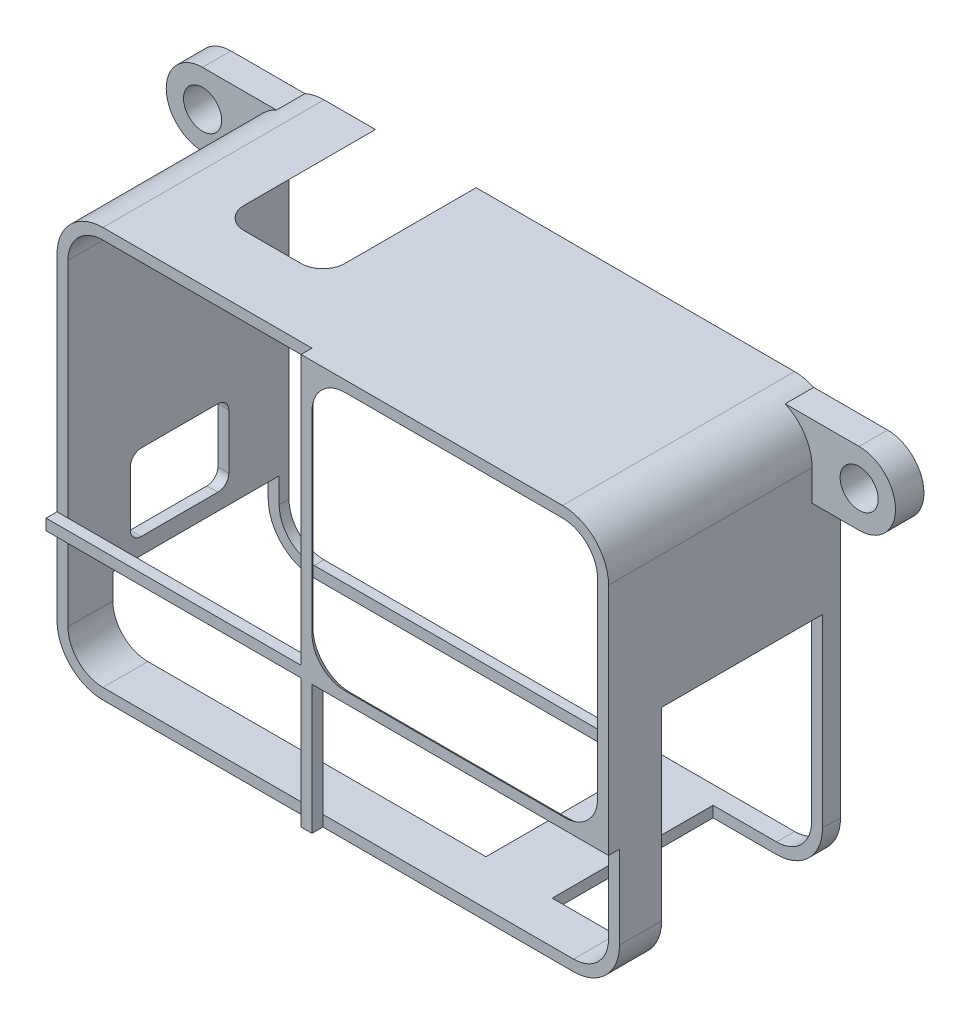
SolidWorks part; units mm, degrees
material "ABS"
ref_plane "Front Plane" through (0, 0, 0) normal (0, 0, 1) x (1, 0, 0)
ref_plane "Top Plane" through (0, 0, 0) normal (0, 1, 0) x (1, 0, 0)
ref_plane "Right Plane" through (0, 0, 0) normal (1, 0, 0) x (0, 0, -1)
sketch "Sketch2" plane through (0, 0, 0) normal (0, 0, 1) x (1, 0, 0)
  line L0 (-27.305, -22.479) -> (27.305, -22.479)
  line L1 (-27.305, -22.225) -> (27.305, -22.225) construction
  line L2 (-31.115, -18.415) -> (-31.115, 18.415) construction
  line L3 (-27.305, 22.225) -> (27.305, 22.225) construction
  line L4 (31.115, -18.415) -> (31.115, 18.415) construction
  line L5 (-31.115, -22.225) -> (31.115, 22.225) construction
  line L6 (-31.115, 22.225) -> (31.115, -22.225) construction
  line L7 (31.369, -18.415) -> (31.369, 18.415)
  line L8 (-27.305, 22.479) -> (27.305, 22.479)
  line L9 (-31.369, -18.415) -> (-31.369, 18.415)
  line L10 (-27.305, -23.749) -> (27.305, -23.749)
  line L11 (32.639, -18.415) -> (32.639, 18.415)
  line L12 (-27.305, 23.749) -> (27.305, 23.749)
  line L13 (-32.639, -18.415) -> (-32.639, 18.415)
  arc A0 (27.305, -22.225) -> (31.115, -18.415) centre (27.305, -18.415) ccw construction
  arc A1 (-27.305, -22.225) -> (-31.115, -18.415) centre (-27.305, -18.415) cw construction
  arc A2 (-31.115, 18.415) -> (-27.305, 22.225) centre (-27.305, 18.415) cw construction
  arc A3 (27.305, 22.225) -> (31.115, 18.415) centre (27.305, 18.415) cw construction
  arc A4 (27.305, -22.479) -> (31.369, -18.415) centre (27.305, -18.415) ccw
  arc A5 (27.305, 22.479) -> (31.369, 18.415) centre (27.305, 18.415) cw
  arc A6 (-31.369, 18.415) -> (-27.305, 22.479) centre (-27.305, 18.415) cw
  arc A7 (-27.305, -22.479) -> (-31.369, -18.415) centre (-27.305, -18.415) cw
  arc A8 (27.305, -23.749) -> (32.639, -18.415) centre (27.305, -18.415) ccw
  arc A9 (27.305, 23.749) -> (32.639, 18.415) centre (27.305, 18.415) cw
  arc A10 (-32.639, 18.415) -> (-27.305, 23.749) centre (-27.305, 18.415) cw
  arc A11 (-27.305, -23.749) -> (-32.639, -18.415) centre (-27.305, -18.415) cw
  point P0 (0, 0)
  dimension "D1" = 3.81
  dimension "D2" = 62.23
  dimension "D3" = 44.45
  dimension "D5" = 1.27
extrude "Boss-Extrude1" add sketch "Sketch2" along normal blind 25.654
sketch "Sketch3" plane through (0, 0, 25.654) normal (0, 0, 1) x (1, 0, 0)
  line L5 (-1.778, 23.749) -> (27.305, 23.749)
  line L6 (-3.048, 23.749) -> (-3.048, -7.493)
  line L7 (27.305, 23.749) -> (-27.305, 23.749) construction
  line L8 (-3.048, -7.493) -> (-32.639, -7.493)
  line L9 (-32.639, 18.415) -> (-32.639, -18.415) construction
  line L11 (-32.639, -8.763) -> (-3.048, -8.763)
  line L12 (-3.048, -8.763) -> (-3.048, -23.749)
  line L13 (-27.305, -23.749) -> (27.305, -23.749) construction
  line L14 (-3.048, -23.749) -> (-1.778, -23.749)
  line L15 (-1.778, -23.749) -> (-1.778, -8.763)
  line L16 (-1.778, -8.763) -> (32.639, -8.763)
  line L17 (32.639, -18.415) -> (32.639, 18.415) construction
  line L18 (32.639, -8.763) -> (32.639, -7.493)
  line L19 (27.559, -7.493) -> (2.032, -7.493)
  line L20 (-1.778, -3.683) -> (-1.778, 18.669)
  line L21 (-1.778, 23.749) -> (-3.048, 23.749)
  line L23 (2.032, 22.479) -> (27.305, 22.479)
  line L26 (-27.305, -23.749) -> (27.305, -23.749)
  line L27 (32.639, -18.415) -> (32.639, 18.415)
  line L28 (27.305, 23.749) -> (-27.305, 23.749)
  line L29 (-32.639, 18.415) -> (-32.639, -18.415)
  line L33 (-32.639, -7.493) -> (-32.639, -8.763)
  line L34 (31.369, 18.415) -> (31.369, -3.683)
  line L36 (32.639, 18.415) -> (32.639, -7.493)
  arc A0 (31.369, 18.415) -> (27.305, 22.479) centre (27.305, 18.415) ccw
  arc A1 (32.639, 18.415) -> (27.305, 23.749) centre (27.305, 18.415) ccw
  arc A2 (31.369, -3.683) -> (27.559, -7.493) centre (27.559, -3.683) cw
  arc A3 (2.032, -7.493) -> (-1.778, -3.683) centre (2.032, -3.683) cw
  arc A4 (-32.639, -18.415) -> (-27.305, -23.749) centre (-27.305, -18.415) ccw
  arc A5 (27.305, -23.749) -> (32.639, -18.415) centre (27.305, -18.415) ccw
  arc A6 (32.639, 18.415) -> (27.305, 23.749) centre (27.305, 18.415) ccw
  arc A7 (-27.305, 23.749) -> (-32.639, 18.415) centre (-27.305, 18.415) ccw
  arc A10 (-1.778, 18.669) -> (2.032, 22.479) centre (2.032, 18.669) cw
  dimension "D6" = 3.81
  dimension "D1" = 1.27
  dimension "D2" = 1.27
  dimension "D3" = 31.242
  dimension "D4" = 34.417
extrude "Boss-Extrude2" add sketch "Sketch3" along normal blind 1.27
sketch "Sketch5" plane through (0, 23.749, 0) normal (0, 1, 0) x (1, 0, 0)
  line L2 (-21.336, 0) -> (-21.336, -15.24)
  line L3 (-18.796, -17.78) -> (-12.192, -17.78)
  line L4 (-9.652, 0) -> (-9.652, -15.24)
  line L5 (-32.639, -25.654) -> (-32.639, 0) construction
  line L6 (27.305, 0) -> (-27.305, 0) construction
  line L7 (-21.336, 0) -> (-9.652, 0)
  arc A0 (-12.192, -17.78) -> (-9.652, -15.24) centre (-12.192, -15.24) ccw
  arc A1 (-21.336, -15.24) -> (-18.796, -17.78) centre (-18.796, -15.24) ccw
  point P7 (-15.494, -17.78)
  point P11 (-9.652, -17.78)
  point P14 (-21.336, -17.78)
  dimension "D4" = 2.54
  dimension "D1" = 11.684
  dimension "D3" = 17.145
  dimension "D2" = 17.78
extrude "Cut-Extrude1" cut sketch "Sketch5" against normal up to next
sketch "Sketch6" plane through (-32.639, 0, 0) normal (-1, 0, 0) x (0, 0, 1)
  line L1 (8.255, -4.699) -> (17.145, -4.699)
  line L2 (6.985, -5.969) -> (6.985, -12.319)
  line L3 (8.255, -13.589) -> (17.145, -13.589)
  line L4 (18.415, -5.969) -> (18.415, -12.319)
  line L6 (25.654, -23.749) -> (0, -23.749) construction
  line L7 (0, 18.415) -> (0, -18.415) construction
  arc A0 (6.985, -12.319) -> (8.255, -13.589) centre (8.255, -12.319) ccw
  arc A1 (8.255, -4.699) -> (6.985, -5.969) centre (8.255, -5.969) ccw
  arc A2 (17.145, -4.699) -> (18.415, -5.969) centre (17.145, -5.969) cw
  arc A3 (17.145, -13.589) -> (18.415, -12.319) centre (17.145, -12.319) ccw
  point P12 (6.985, -4.699)
  point P15 (18.415, -4.699)
  point P18 (18.415, -13.589)
  point P19 (18.415, -9.144)
  point P20 (12.7, -4.699)
  dimension "D5" = 1.27
  dimension "D1" = 11.43
  dimension "D2" = 8.89
  dimension "D3" = 12.7
  dimension "D4" = 14.605
extrude "Cut-Extrude2" cut sketch "Sketch6" against normal up to next
sketch "Sketch7" plane through (0, -23.749, 0) normal (0, -1, 0) x (1, 0, 0)
  line L0 (-32.639, 25.654) -> (-32.639, 0) construction
  line L1 (-32.639, 1.143) -> (11.938, 1.143)
  line L2 (-32.639, 1.143) -> (-32.639, 20.447)
  line L3 (-32.639, 20.447) -> (11.938, 20.447)
  line L4 (11.938, 1.143) -> (11.938, 20.447)
  line L5 (-27.305, 0) -> (27.305, 0) construction
  point P6 (11.938, 10.795)
  dimension "D1" = 44.577
  dimension "D2" = 19.304
  dimension "D3" = 10.795
extrude "Cut-Extrude3" cut sketch "Sketch7" against normal blind 8.255
sketch "Sketch8" plane through (32.639, 0, 0) normal (1, 0, 0) x (0, 0, -1)
  line L0 (-25.654, -23.749) -> (0, -23.749) construction
  line L1 (-20.7645, -23.749) -> (-2.0955, -23.749)
  line L2 (-20.7645, -23.749) -> (-20.7645, 3.048)
  line L3 (-20.7645, 3.048) -> (-2.0955, 3.048)
  line L4 (-2.0955, -23.749) -> (-2.0955, 3.048)
  line L5 (0, -18.415) -> (0, 18.415) construction
  point P6 (-11.43, 3.048)
  dimension "D1" = 18.669
  dimension "D2" = 26.797
  dimension "D3" = 11.43
extrude "Cut-Extrude4" cut sketch "Sketch8" against normal blind 12.7
fillet "Fillet2" radius 2.54 3 edges at (-0.6621, 21.3631, 25.654) (-0.6621, -6.3771, 25.654) (30.2531, -6.3771, 25.654)
sketch "Sketch9" plane through (0, 0, 0) normal (0, 0, 1) x (1, 0, 0)
  line L0 (-29.5221, 23.2664) -> (-38.1, 23.2664)
  line L31 (-38.1, 14.8336) -> (-32.639, 14.8336)
  line L32 (-32.639, 18.415) -> (-32.639, -7.493) construction
  line L33 (-32.639, 14.8336) -> (-32.639, 18.415)
  line L34 (0, -14.8082) -> (0, 14.8082) construction
  line L35 (29.5221, 23.2664) -> (38.1, 23.2664)
  line L36 (32.639, 14.8336) -> (32.639, 18.415)
  line L37 (38.1, 14.8336) -> (32.639, 14.8336)
  line L38 (14.8082, 0) -> (-14.8082, 0) construction
  line L39 (-29.5221, -23.2664) -> (-38.1, -23.2664) construction
  line L40 (-32.639, -14.8336) -> (-32.639, -18.415) construction
  line L41 (-38.1, -14.8336) -> (-32.639, -14.8336) construction
  arc A12 (-27.305, 23.749) -> (-32.639, 18.415) centre (-27.305, 18.415) ccw construction
  arc A13 (-32.639, 18.415) -> (-29.5221, 23.2664) centre (-27.305, 18.415) cw
  arc A14 (-38.1, 23.2664) -> (-38.1, 14.8336) centre (-38.1, 19.05) ccw
  circle A15 centre (-38.1, 19.05) radius 2.2098
  arc A16 (32.639, 18.415) -> (29.5221, 23.2664) centre (27.305, 18.415) ccw
  arc A17 (38.1, 23.2664) -> (38.1, 14.8336) centre (38.1, 19.05) cw
  circle A18 centre (38.1, 19.05) radius 2.2098
  circle A19 centre (-38.1, -19.05) radius 2.2098 construction
  arc A20 (-32.639, -18.415) -> (-29.5221, -23.2664) centre (-27.305, -18.415) ccw construction
  arc A21 (-38.1, -23.2664) -> (-38.1, -14.8336) centre (-38.1, -19.05) cw construction
  dimension "D1" = 4.2164
  dimension "D2" = 4.4196
  dimension "D3" = 76.2
  dimension "D4" = 38.1
extrude "Boss-Extrude3" add sketch "Sketch9" along normal blind 3.302
chamfer "Chamfer1" distance 1.27 angle 45 5 edges at (-21.336, 22.479, 7.62) (-20.5921, 22.479, 17.0361) (-15.494, 22.479, 17.78) (-10.3959, 22.479, 17.0361) (-9.652, 22.479, 7.62)
equation "\"tolerance\"= .005"
equation "\"D4@Sketch2\" = \"tolerance\" * 2"
equation "\"D1@Boss-Extrude1\"= 1 + \"tolerance\" * 2"
equation "\"D3@Sketch3\"=1.225+\"tolerance\""
equation "\"D4@Sketch3\"=1.35+\"tolerance\""
equation "\"D1@Sketch5\"=0.45+\"tolerance\"*2"
equation "\"D2@Sketch7\"=0.75+\"tolerance\"*2"
equation "\"D1@Sketch7\"=1.75+\"tolerance\""
equation "\"D1@Sketch8\"=.725+\"tolerance\"*2"
equation "\"D2@Sketch8\"=1.05+\"tolerance\""
equation "\"D1@Cut-Extrude3\"= 0.140000in + \"tolerance\""
equation "\"D1@Cut-Extrude4\"=.5"
equation "\"D1@Boss-Extrude3\"= .125 + \"tolerance\""
equation "\"D1@Sketch9\"=(.322 + \"tolerance\" * 2)/2"
equation "\"D2@Sketch9\"=.164 + \"tolerance\" * 2"
